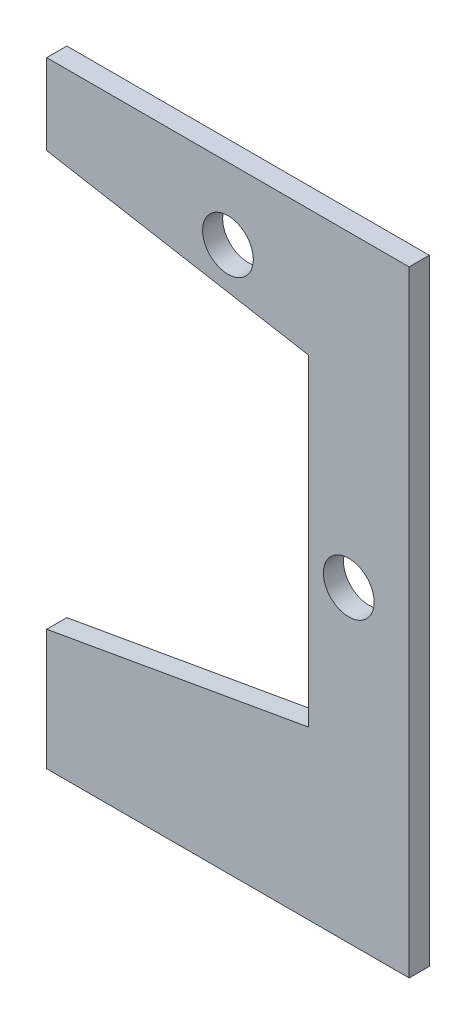
SolidWorks part; units mm, degrees
material "Balsa"
ref_plane "Plan de face" through (0, 0, 0) normal (0, 0, 1) x (1, 0, 0)
ref_plane "Plan de dessus" through (0, 0, 0) normal (0, 1, 0) x (1, 0, 0)
ref_plane "Plan de droite" through (0, 0, 0) normal (1, 0, 0) x (0, 0, -1)
sketch "Esquisse1" plane through (0, 0, 0) normal (0, 0, 1) x (1, 0, 0)
  line L0 (-65, 51.4613) -> (0, 40)
  line L1 (0, 40) -> (0, -40)
  line L2 (-65, -51.4613) -> (0, -40)
  line L4 (-65, -51.4613) -> (-65, -81.4613)
  line L5 (-65, -81.4613) -> (25, -81.4613)
  line L6 (25, -81.4613) -> (25, 71.4613)
  line L7 (25, 71.4613) -> (-65, 71.4613)
  line L8 (-65, 71.4613) -> (-65, 51.4613)
  circle A0 centre (-20, 53.6808) radius 6.3
  circle A1 centre (10, -5) radius 6.3
  dimension "D1" = 12.6
  dimension "D13" = 12.6
  dimension "D2" = 10
  dimension "D3" = 20
  dimension "D4" = 80
  dimension "D5" = 65
  dimension "D6" = 100
  dimension "D7" = 100
  dimension "D8" = 20
  dimension "D9" = 30
  dimension "D10" = 90
  dimension "D11" = 10
  dimension "D12" = 35
extrude "Boss.-Extru.1" add sketch "Esquisse1" along normal blind 5
